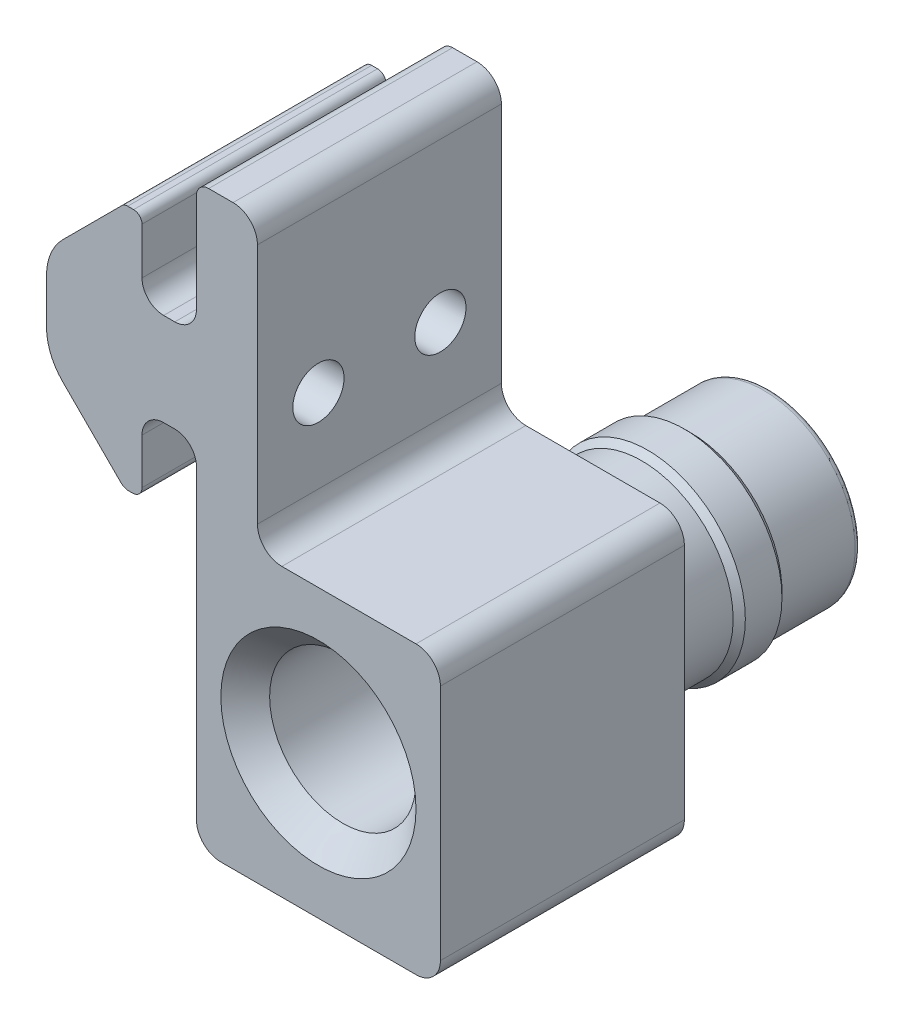
SolidWorks part; units mm, degrees
ref_plane "Front Plane" through (0, 0, 0) normal (0, 0, 1) x (1, 0, 0)
ref_plane "Top Plane" through (0, 0, 0) normal (0, 1, 0) x (1, 0, 0)
ref_plane "Right Plane" through (0, 0, 0) normal (1, 0, 0) x (0, 0, -1)
sketch "Sketch1" plane through (0, 0, 0) normal (0, 0, 1) x (1, 0, 0)
  line L0 (38.3, 9.8814) -> (38.3, 10.7456)
  line L1 (38.3, 27.3535) -> (38.3, 28.2156)
  line L2 (39.3, 33.711) -> (41.3, 33.711)
  line L3 (33.836, 28.448) -> (33.836, 24.6302)
  line L9 (51.3, -13.6057) -> (40.3, -13.6057)
  line L11 (38.3, -11.6057) -> (38.3, 5.3943)
  line L13 (43.3, 11.8814) -> (43.3, 31.711)
  line L14 (45.3, 9.8814) -> (56.3, 9.8814)
  line L15 (58.3, 7.8814) -> (58.3, -11.6057)
  line L16 (56.3, -13.6057) -> (51.3, -13.6057)
  line L327 (33.836, 28.448) -> (33.836, 24.6302)
  line L328 (35.6108, 22.8554) -> (36.5252, 22.8554)
  line L329 (38.3, 24.6302) -> (38.3, 27.3535)
  line L330 (38.3, 28.2156) -> (38.3, 32.711)
  line L426 (38.3, 5.3943) -> (38.3, 9.8814)
  line L427 (38.3, 10.7456) -> (38.3, 13.4698)
  line L428 (36.5252, 15.2446) -> (35.6108, 15.2446)
  line L429 (33.836, 13.4698) -> (33.836, 9.7387)
  line L430 (33.0603, 8.963) -> (32.7869, 8.963)
  line L431 (32.0904, 9.2515) -> (27.339, 14.0029)
  line L432 (26.0064, 17.2201) -> (26.0064, 20.8799)
  line L433 (27.339, 24.0971) -> (32.1771, 28.9352)
  line L434 (32.6643, 29.137) -> (33.147, 29.137)
  arc A0 (38.3, -11.6057) -> (40.3, -13.6057) centre (40.3, -11.6057) ccw
  arc A1 (56.3, -13.6057) -> (58.3, -11.6057) centre (56.3, -11.6057) ccw
  arc A2 (39.3, 33.711) -> (38.3, 32.711) centre (39.3, 32.711) ccw
  arc A3 (58.3, 7.8814) -> (56.3, 9.8814) centre (56.3, 7.8814) ccw
  arc A4 (45.3, 9.8814) -> (43.3, 11.8814) centre (45.3, 11.8814) cw
  arc A5 (43.3, 31.711) -> (41.3, 33.711) centre (41.3, 31.711) ccw
  arc A360 (33.836, 28.448) -> (33.147, 29.137) centre (33.147, 28.448) ccw
  arc A361 (33.836, 24.6302) -> (35.6108, 22.8554) centre (35.6108, 24.6302) ccw
  arc A362 (36.5252, 22.8554) -> (38.3, 24.6302) centre (36.5252, 24.6302) ccw
  arc A473 (38.3, 13.4698) -> (36.5252, 15.2446) centre (36.5252, 13.4698) ccw
  arc A474 (35.6108, 15.2446) -> (33.836, 13.4698) centre (35.6108, 13.4698) ccw
  arc A475 (33.0603, 8.963) -> (33.836, 9.7387) centre (33.0603, 9.7387) ccw
  arc A476 (32.0904, 9.2515) -> (32.7869, 8.963) centre (32.7869, 9.9481) ccw
  arc A477 (26.0064, 17.2201) -> (27.339, 14.0029) centre (30.5562, 17.2201) ccw
  arc A478 (27.339, 24.0971) -> (26.0064, 20.8799) centre (30.5562, 20.8799) ccw
  arc A479 (32.6643, 29.137) -> (32.1771, 28.9352) centre (32.6643, 28.448) ccw
  dimension "D1" = 2
  dimension "D2" = 2
  dimension "D3" = 1
extrude "Boss-Extrude1" add sketch "Sketch1" against normal blind 20 contours L434 A479 L433 A478 L432 A477 L431 A476 L430 A475 L429 A474 L428 A473 L427 L0 L426 L2 L330 L1 L329 A362 L328 A361 L3 A360 region at (43.6881, 6.2552, 0)
sketch "Sketch3" plane through (43.3, 0, 0) normal (1, 0, 0) x (0, 0, -1)
  circle A0 centre (5, 18.711) radius 2.1
  circle A1 centre (15, 18.711) radius 2.1
extrude "Cut-Extrude1" cut sketch "Sketch3" against normal through all
sketch "Sketch4" plane through (0, 0, -20) normal (0, 0, -1) x (-1, 0, 0)
  circle A0 centre (-48.3, -1.8621) radius 7.5
extrude "Boss-Extrude2" add sketch "Sketch4" along normal blind 7
sketch "Sketch5" plane through (0, 0, -27) normal (0, 0, -1) x (-1, 0, 0)
  circle A0 centre (-48.3, -1.8621) radius 8
extrude "Boss-Extrude3" add sketch "Sketch5" along normal blind 3
sketch "Sketch6" plane through (0, 0, -30) normal (0, 0, -1) x (-1, 0, 0)
  circle A1 centre (-48.3, -1.8621) radius 7.5
extrude "Boss-Extrude4" add sketch "Sketch6" along normal blind 7
sketch "Sketch7" plane through (0, 0, -37) normal (0, 0, -1) x (-1, 0, 0)
  circle A0 centre (-48.3, -1.8621) radius 6
extrude "Cut-Extrude2" cut sketch "Sketch7" against normal through all
fillet "Fillet1" radius 1 1 edges at (55.8, -1.8621, -20)
chamfer "Chamfer1" distance 0.5 angle 45 2 edges at (40.8, -1.8621, -27) (40.8, -1.8621, -30)
chamfer "Chamfer2" distance 2 angle 45 1 edges at (42.3, -1.8621, 0)
fillet "Fillet2" radius 0.5 2 edges at (40.8, -1.8621, -37) (42.3, -1.8621, -37)
